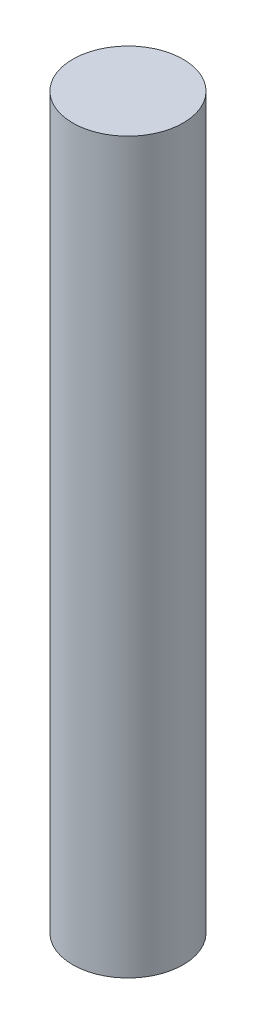
SolidWorks part; units mm, degrees
ref_plane "Front Plane" through (0, 0, 0) normal (0, 0, 1) x (1, 0, 0)
ref_plane "Top Plane" through (0, 0, 0) normal (0, 1, 0) x (1, 0, 0)
ref_plane "Right Plane" through (0, 0, 0) normal (1, 0, 0) x (0, 0, -1)
sketch "Sketch1" plane through (0, 0, 0) normal (0, 1, 0) x (1, 0, 0)
  circle A0 centre (0, 0) radius 5
  dimension "D1" = 10
extrude "Boss-Extrude1" add sketch "Sketch1" along normal blind 66
